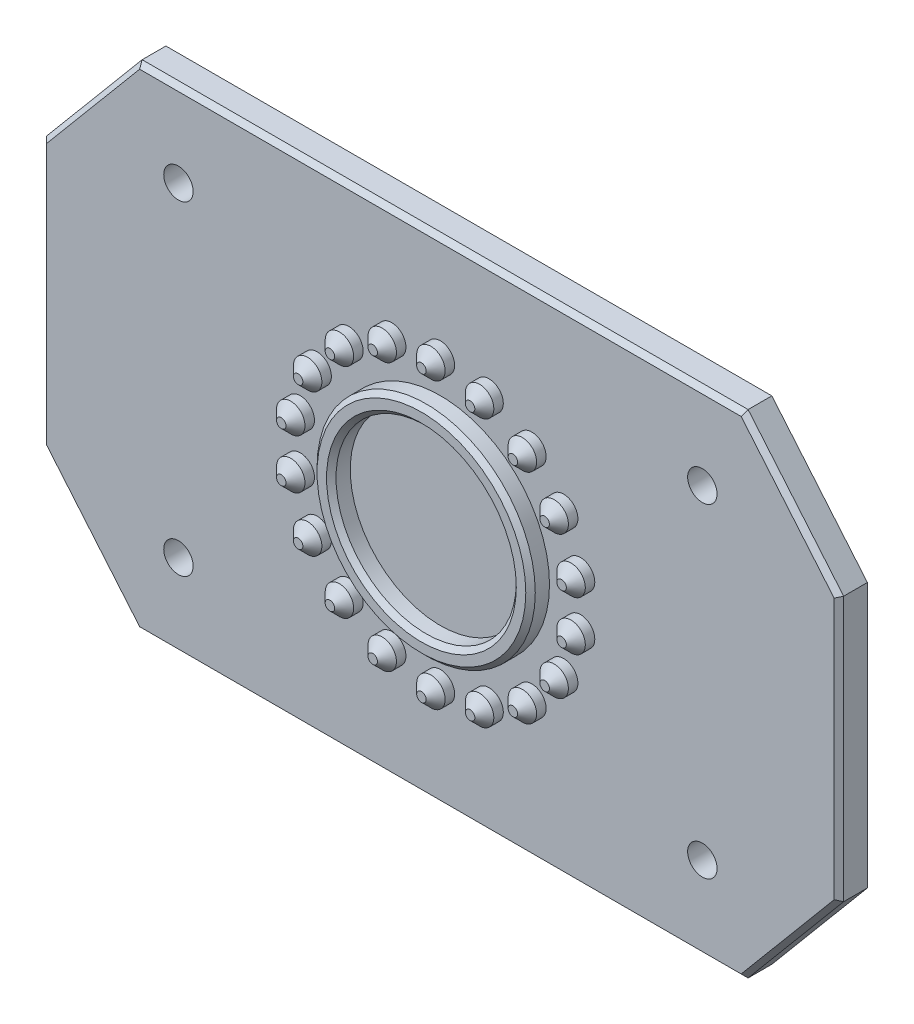
SolidWorks part; units mm, degrees
ref_plane "Front Plane" through (0, 0, 0) normal (0, 0, 1) x (1, 0, 0)
ref_plane "Top Plane" through (0, 0, 0) normal (0, 1, 0) x (1, 0, 0)
ref_plane "Right Plane" through (0, 0, 0) normal (1, 0, 0) x (0, 0, -1)
sketch "Sketch1" plane through (0, 0, 0) normal (0, 0, 1) x (1, 0, 0)
  line L0 (-110, 14.6505) -> (-99.9308, 2.6505) construction
  line L6 (-99.9308, 54.5343) -> (-110, 42.5343) construction
  line L7 (-110, 42.5343) -> (-110, 14.6505) construction
  line L8 (-26, 14.6505) -> (-26, 42.5343) construction
  line L9 (-26, 42.5343) -> (-36.0692, 54.5343) construction
  line L15 (-36.0692, 2.6505) -> (-26, 14.6505) construction
  line L16 (-110, 14.6505) -> (-99.9308, 2.6505)
  line L22 (-99.9308, 54.5343) -> (-110, 42.5343)
  line L23 (-110, 42.5343) -> (-110, 14.6505)
  line L24 (-26, 14.6505) -> (-26, 42.5343)
  line L25 (-26, 42.5343) -> (-36.0692, 54.5343)
  line L31 (-36.0692, 2.6505) -> (-26, 14.6505)
  line L32 (-99.9308, 54.5343) -> (-36.0692, 54.5343)
  line L33 (-99.9308, 2.6505) -> (-36.0692, 2.6505)
  circle A0 centre (-68, 28.5924) radius 9.5 construction
  circle A1 centre (-68, 28.5924) radius 9.5
extrude "Boss-Extrude1" add sketch "Sketch1" along normal blind 3 contours A1 | L16 L33 L31 L24 L25 L32 L22 L23 A1 region at (-109.0127, 28.5924, 0) region at (-68, 28.5924, 0)
chamfer "Chamfer1" distance 0.5 angle 45 8 edges at (-110, 28.5924, 3) (-104.9654, 48.5343, 3) (-68, 54.5343, 3) (-31.0346, 48.5343, 3) (-26, 28.5924, 3) (-31.0346, 8.6505, 3) (-68, 2.6505, 3) (-104.9654, 8.6505, 3)
sketch "Sketch2" plane through (0, 0, 0) normal (0, 0, -1) x (-1, 0, 0)
  circle A0 centre (40.3924, 45.6851) radius 1.55 construction
  circle A1 centre (95.6076, 45.6851) radius 1.55 construction
  circle A2 centre (95.6076, 11.4997) radius 1.55 construction
  circle A3 centre (40.3924, 11.4997) radius 1.55 construction
  circle A4 centre (40.3924, 45.6851) radius 1.55
  circle A5 centre (95.6076, 45.6851) radius 1.55
  circle A6 centre (95.6076, 11.4997) radius 1.55
  circle A7 centre (40.3924, 11.4997) radius 1.55
extrude "Cut-Extrude1" cut sketch "Sketch2" against normal up to next
sketch "Sketch3" plane through (0, 0, 3) normal (0, 0, 1) x (1, 0, 0)
  line L0 (-68, 28.5924) -> (-68, 43.5924) construction
  line L8 (-99.9308, 2.6505) -> (-36.0692, 2.6505)
  line L9 (-110, 14.6505) -> (-99.9308, 2.6505)
  line L10 (-110, 42.5343) -> (-110, 14.6505)
  line L11 (-99.9308, 54.5343) -> (-110, 42.5343)
  line L12 (-36.0692, 54.5343) -> (-99.9308, 54.5343)
  line L13 (-26, 42.5343) -> (-36.0692, 54.5343)
  line L14 (-26, 14.6505) -> (-26, 42.5343)
  line L15 (-36.0692, 2.6505) -> (-26, 14.6505)
  line L16 (-99.9308, 2.6505) -> (-36.0692, 2.6505)
  line L17 (-110, 14.6505) -> (-99.9308, 2.6505)
  line L18 (-110, 42.5343) -> (-110, 14.6505)
  line L19 (-99.9308, 54.5343) -> (-110, 42.5343)
  line L20 (-36.0692, 54.5343) -> (-99.9308, 54.5343)
  line L21 (-26, 42.5343) -> (-36.0692, 54.5343)
  line L22 (-26, 14.6505) -> (-26, 42.5343)
  line L23 (-36.0692, 2.6505) -> (-26, 14.6505)
  circle A0 centre (-68, 43.5924) radius 1.5
  circle A1 centre (-68, 28.5924) radius 9.5
  circle A2 centre (-68, 28.5924) radius 9.5
  circle A3 centre (-62.8697, 42.6878) radius 1.5
  circle A4 centre (-58.3582, 40.0831) radius 1.5
  circle A5 centre (-55.0096, 36.0924) radius 1.5
  circle A6 centre (-53.2279, 31.1971) radius 1.5
  circle A7 centre (-53.2279, 25.9877) radius 1.5
  circle A8 centre (-55.0096, 21.0924) radius 1.5
  circle A9 centre (-58.3582, 17.1017) radius 1.5
  circle A10 centre (-62.8697, 14.497) radius 1.5
  circle A11 centre (-68, 13.5924) radius 1.5
  circle A12 centre (-73.1303, 14.497) radius 1.5
  circle A13 centre (-77.6418, 17.1017) radius 1.5
  circle A14 centre (-80.9904, 21.0924) radius 1.5
  circle A15 centre (-82.7721, 25.9877) radius 1.5
  circle A16 centre (-82.7721, 31.1971) radius 1.5
  circle A17 centre (-80.9904, 36.0924) radius 1.5
  circle A18 centre (-77.6418, 40.0831) radius 1.5
  circle A19 centre (-73.1303, 42.6878) radius 1.5
  point P50 (-68, 28.5924)
  dimension "D4" = 3
  dimension "D3" = 15
  dimension "D1" = 0
  dimension "D2" = 0
  dimension "D5" = 18
extrude "Boss-Extrude2" add sketch "Sketch3" along normal blind 2 contours A19 | A0 | A3 | A4 | A5 | A6 | A7 | A8 | A9 | A10 | A11 | A13 | A14 | A15 | A16 | A17 | A18 | A12 region at (-68, 43.5924, 3) region at (-62.8697, 42.6878, 3) region at (-58.3582, 40.0831, 3) region at (-55.0096, 36.0924, 3) region at (-53.2279, 31.1971, 3) region at (-53.2279, 25.9877, 3) region at (-55.0096, 21.0924, 3) region at (-58.3582, 17.1017, 3) region at (-62.8697, 14.497, 3) region at (-68, 13.5924, 3) region at (-77.6418, 17.1017, 3) region at (-80.9904, 21.0924, 3) region at (-82.7721, 25.9877, 3) region at (-82.7721, 31.1971, 3) region at (-80.9904, 36.0924, 3) region at (-73.1303, 42.6878, 3)
chamfer "Chamfer2" distance 1 angle 45 18 edges at (-66.5, 43.5924, 5) (-79.4904, 36.0924, 5) (-81.2721, 31.1971, 5) (-81.2721, 25.9877, 5) (-79.4904, 21.0924, 5) (-76.1418, 17.1017, 5) (-71.6303, 14.497, 5) (-66.5, 13.5924, 5) (-61.3697, 14.497, 5) (-56.8582, 17.1017, 5) (-53.5096, 21.0924, 5) (-51.7279, 25.9877, 5) (-51.7279, 31.1971, 5) (-53.5096, 36.0924, 5) (-56.8582, 40.0831, 5) (-61.3697, 42.6878, 5) (-71.6303, 42.6878, 5) (-76.1418, 40.0831, 5)
sketch "Sketch4" plane through (0, 0, 3) normal (0, 0, 1) x (1, 0, 0)
  line L8 (-99.9308, 2.6505) -> (-36.0692, 2.6505)
  line L9 (-36.0692, 2.6505) -> (-26, 14.6505)
  line L10 (-26, 14.6505) -> (-26, 42.5343)
  line L11 (-26, 42.5343) -> (-36.0692, 54.5343)
  line L12 (-36.0692, 54.5343) -> (-99.9308, 54.5343)
  line L13 (-99.9308, 54.5343) -> (-110, 42.5343)
  line L14 (-110, 42.5343) -> (-110, 14.6505)
  line L15 (-110, 14.6505) -> (-99.9308, 2.6505)
  line L16 (-99.9308, 2.6505) -> (-36.0692, 2.6505)
  line L17 (-36.0692, 2.6505) -> (-26, 14.6505)
  line L18 (-26, 14.6505) -> (-26, 42.5343)
  line L19 (-26, 42.5343) -> (-36.0692, 54.5343)
  line L20 (-36.0692, 54.5343) -> (-99.9308, 54.5343)
  line L21 (-99.9308, 54.5343) -> (-110, 42.5343)
  line L22 (-110, 42.5343) -> (-110, 14.6505)
  line L23 (-110, 14.6505) -> (-99.9308, 2.6505)
  circle A0 centre (-68, 28.5924) radius 11.5
  circle A1 centre (-68, 28.5924) radius 9.5
  circle A2 centre (-68, 28.5924) radius 9.5
  circle A3 centre (-68, 43.5924) radius 1.5
  circle A4 centre (-68, 43.5924) radius 1.5
  circle A5 centre (-62.8697, 14.497) radius 1.5
  circle A6 centre (-62.8697, 14.497) radius 1.5
  circle A7 centre (-58.3582, 17.1017) radius 1.5
  circle A8 centre (-58.3582, 17.1017) radius 1.5
  circle A9 centre (-55.0096, 21.0924) radius 1.5
  circle A10 centre (-55.0096, 21.0924) radius 1.5
  circle A11 centre (-53.2279, 25.9877) radius 1.5
  circle A12 centre (-53.2279, 25.9877) radius 1.5
  circle A13 centre (-53.2279, 31.1971) radius 1.5
  circle A14 centre (-53.2279, 31.1971) radius 1.5
  circle A15 centre (-55.0096, 36.0924) radius 1.5
  circle A16 centre (-55.0096, 36.0924) radius 1.5
  circle A17 centre (-58.3582, 40.0831) radius 1.5
  circle A18 centre (-58.3582, 40.0831) radius 1.5
  circle A19 centre (-62.8697, 42.6878) radius 1.5
  circle A20 centre (-62.8697, 42.6878) radius 1.5
  circle A21 centre (-77.6418, 40.0831) radius 1.5
  circle A22 centre (-77.6418, 40.0831) radius 1.5
  circle A23 centre (-80.9904, 36.0924) radius 1.5
  circle A24 centre (-80.9904, 36.0924) radius 1.5
  circle A25 centre (-82.7721, 31.1971) radius 1.5
  circle A26 centre (-82.7721, 31.1971) radius 1.5
  circle A27 centre (-82.7721, 25.9877) radius 1.5
  circle A28 centre (-82.7721, 25.9877) radius 1.5
  circle A29 centre (-80.9904, 21.0924) radius 1.5
  circle A30 centre (-80.9904, 21.0924) radius 1.5
  circle A31 centre (-77.6418, 17.1017) radius 1.5
  circle A32 centre (-77.6418, 17.1017) radius 1.5
  circle A33 centre (-73.1303, 14.497) radius 1.5
  circle A34 centre (-73.1303, 14.497) radius 1.5
  circle A35 centre (-68, 13.5924) radius 1.5
  circle A36 centre (-68, 13.5924) radius 1.5
  circle A37 centre (-73.1303, 42.6878) radius 1.5
  circle A38 centre (-73.1303, 42.6878) radius 1.5
  dimension "D21" = 2
  dimension "D1" = 0
  dimension "D2" = 0
  dimension "D3" = 0
  dimension "D4" = 0
  dimension "D5" = 0
  dimension "D6" = 0
  dimension "D7" = 0
  dimension "D8" = 0
  dimension "D9" = 0
  dimension "D10" = 0
  dimension "D11" = 0
  dimension "D12" = 0
  dimension "D13" = 0
  dimension "D14" = 0
  dimension "D15" = 0
  dimension "D16" = 0
  dimension "D17" = 0
  dimension "D18" = 0
  dimension "D19" = 0
  dimension "D20" = 0
extrude "Boss-Extrude3" add sketch "Sketch4" along normal blind 2 contours A0 A2 region at (-79.1747, 28.5924, 3)
chamfer "Chamfer3" distance 0.5 angle 45 2 edges at (-56.5, 28.5924, 5) (-58.5, 28.5924, 5)
